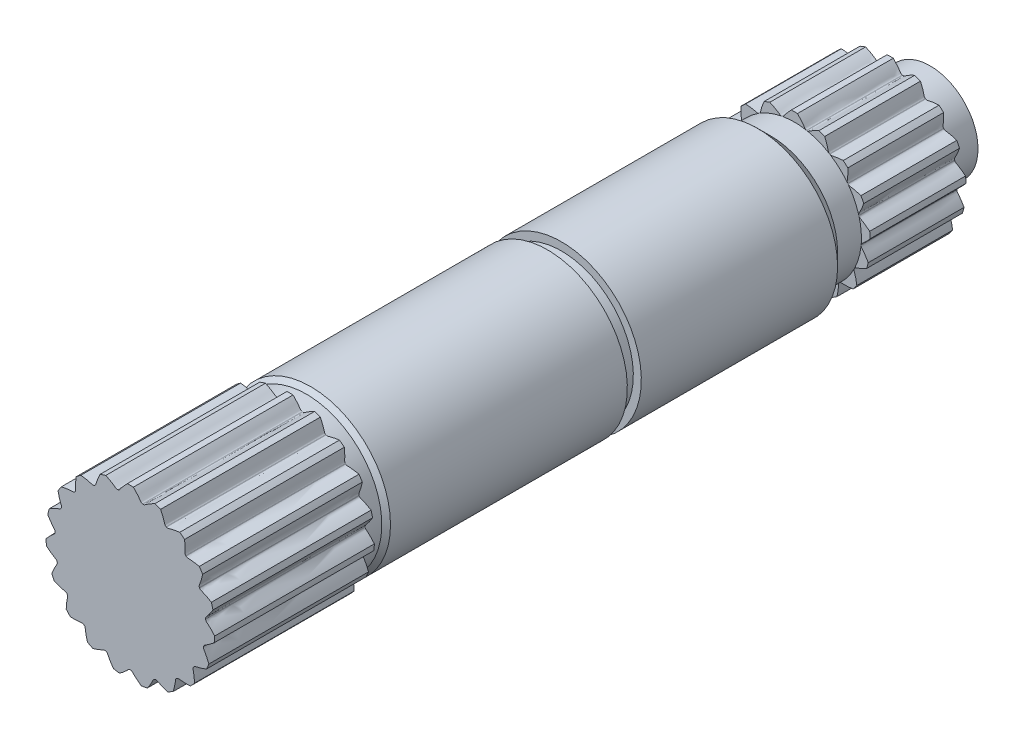
SolidWorks part; units mm, degrees
material "Alloy Steel"
ref_plane "Front Plane" through (0, 0, 0) normal (0, 0, 1) x (1, 0, 0)
ref_plane "Top Plane" through (0, 0, 0) normal (0, 1, 0) x (1, 0, 0)
ref_plane "Right Plane" through (0, 0, 0) normal (1, 0, 0) x (0, 0, -1)
sketch "Sketch12" plane through (0, 0, 0) normal (0, 0, 1) x (1, 0, 0)
  circle A0 centre (0, 0) radius 10
  dimension "D1" = 20
extrude "Shaft" add sketch "Sketch12" along normal mid plane 60
sketch "Sketch13" plane through (0, 0, 30) normal (0, 0, 1) x (1, 0, 0)
  circle A0 centre (0, 0) radius 9.4556
  dimension "D1" = 18.9113
extrude "Motor side relief" add sketch "Sketch13" along normal blind 1.587
sketch "Sketch14" plane through (0, 0, -30) normal (0, 0, -1) x (-1, 0, 0)
  circle A0 centre (0, 0) radius 8.3981
  dimension "D1" = 16.7963
extrude "Gear side relief" add sketch "Sketch14" along normal blind 1.587
sketch "Sketch15" plane through (0, 0, 31.587) normal (0, 0, 1) x (1, 0, 0)
  line L0 (5.7898, -7.4758) -> (5.8078, -7.4618)
  line L1 (5.8078, -7.4618) -> (5.8257, -7.4478)
  line L2 (7.9035, -5.1908) -> (7.9159, -5.1717)
  line L3 (7.9159, -5.1717) -> (7.9284, -5.1527)
  line L4 (9.1607, -2.3432) -> (9.1663, -2.3212)
  line L5 (9.1663, -2.3212) -> (9.1719, -2.2992)
  line L6 (9.4252, 0.7582) -> (9.4233, 0.7808)
  line L7 (9.4233, 0.7808) -> (9.4214, 0.8035)
  line L8 (8.6683, 3.7775) -> (8.6592, 3.7983)
  line L9 (8.6592, 3.7983) -> (8.6501, 3.8191)
  line L10 (6.9721, 6.3874) -> (6.9567, 6.4041)
  line L11 (6.9567, 6.4041) -> (6.9413, 6.4208)
  line L12 (4.5204, 8.3051) -> (4.5004, 8.316)
  line L13 (4.5004, 8.316) -> (4.4804, 8.3268)
  line L14 (1.5788, 9.3229) -> (1.5563, 9.3267)
  line L15 (1.5563, 9.3267) -> (1.5339, 9.3304)
  line L16 (-1.5339, 9.3304) -> (-1.5563, 9.3267)
  line L17 (-1.5563, 9.3267) -> (-1.5788, 9.3229)
  line L18 (-4.4804, 8.3268) -> (-4.5004, 8.316)
  line L19 (-4.5004, 8.316) -> (-4.5204, 8.3051)
  line L20 (-6.9413, 6.4208) -> (-6.9567, 6.4041)
  line L21 (-6.9567, 6.4041) -> (-6.9721, 6.3874)
  line L22 (-8.6501, 3.8191) -> (-8.6592, 3.7983)
  line L23 (-8.6592, 3.7983) -> (-8.6683, 3.7775)
  line L24 (-9.4214, 0.8035) -> (-9.4233, 0.7808)
  line L25 (-9.4233, 0.7808) -> (-9.4252, 0.7582)
  line L26 (-9.1719, -2.2992) -> (-9.1663, -2.3212)
  line L27 (-9.1663, -2.3212) -> (-9.1607, -2.3432)
  line L28 (-7.9284, -5.1527) -> (-7.9159, -5.1717)
  line L29 (-7.9159, -5.1717) -> (-7.9035, -5.1908)
  line L30 (-5.8257, -7.4478) -> (-5.8078, -7.4618)
  line L31 (-5.8078, -7.4618) -> (-5.7898, -7.4758)
  line L32 (-3.0917, -8.9359) -> (-3.0702, -8.9433)
  line L33 (-3.0702, -8.9433) -> (-3.0487, -8.9507)
  line L34 (-0.0227, -9.4556) -> (0, -9.4556)
  line L35 (0, -9.4556) -> (0.0227, -9.4556)
  line L36 (3.0487, -8.9507) -> (3.0702, -8.9433)
  line L37 (3.0702, -8.9433) -> (3.0917, -8.9359)
  arc A0 (4.6925, -9.4774) -> (5.3676, -9.1121) centre (0, 0) ccw
  arc A1 (7.5156, -7.4402) -> (8.0355, -6.8755) centre (0, 0) ccw
  arc A2 (9.5242, -4.5968) -> (9.8326, -3.8939) centre (0, 0) ccw
  arc A3 (10.5007, -1.2552) -> (10.5641, -0.4903) centre (0, 0) ccw
  arc A4 (10.3394, 2.2224) -> (10.1509, 2.9665) centre (0, 0) ccw
  arc A5 (9.0575, 5.4591) -> (8.6377, 6.1017) centre (0, 0) ccw
  arc A6 (6.7942, 8.1043) -> (6.1885, 8.5758) centre (0, 0) ccw
  arc A7 (3.7946, 9.8713) -> (3.0686, 10.1205) centre (0, 0) ccw
  arc A8 (0.3838, 10.5685) -> (-0.3838, 10.5685) centre (0, 0) ccw
  arc A9 (-3.0686, 10.1205) -> (-3.7946, 9.8713) centre (0, 0) ccw
  arc A10 (-6.1885, 8.5758) -> (-6.7942, 8.1043) centre (0, 0) ccw
  arc A11 (-8.6377, 6.1017) -> (-9.0575, 5.4591) centre (0, 0) ccw
  arc A12 (-10.1509, 2.9665) -> (-10.3394, 2.2224) centre (0, 0) ccw
  arc A13 (-10.5641, -0.4903) -> (-10.5007, -1.2552) centre (0, 0) ccw
  arc A14 (-9.8326, -3.8939) -> (-9.5242, -4.5968) centre (0, 0) ccw
  arc A15 (-8.0355, -6.8755) -> (-7.5156, -7.4402) centre (0, 0) ccw
  arc A16 (-5.3676, -9.1121) -> (-4.6925, -9.4774) centre (0, 0) ccw
  arc A17 (-2.1181, -10.3612) -> (-1.361, -10.4876) centre (0, 0) ccw
  arc A18 (1.361, -10.4876) -> (2.1181, -10.3612) centre (0, 0) ccw
  spline S0 degree 3 poles (3.0917, -8.9359) (3.1544, -8.9142) (3.2184, -8.911) (3.3396, -8.938) (3.397, -8.9729) (3.5767, -9.0624) (3.828, -9.1783) (4.24, -9.3384) (4.5379, -9.4334) (4.6925, -9.4774) knots 0 0 0 0 0.125 0.125 0.25 0.25 0.5 0.75 1 1 1 1
  spline S1 degree 3 poles (5.3676, -9.1121) (5.4153, -8.9586) (5.4987, -8.6572) (5.5901, -8.2247) (5.6305, -7.951) (5.6538, -7.7516) (5.656, -7.6845) (5.6997, -7.5682) (5.7374, -7.5164) (5.7898, -7.4758) knots 0 0 0 0 0.25 0.5 0.75 0.75 0.875 0.875 1 1 1 1
  spline S2 degree 3 poles (5.8257, -7.4478) (5.8779, -7.407) (5.9374, -7.3832) (6.0608, -7.3694) (6.1265, -7.3837) (6.3255, -7.41) (6.6008, -7.438) (7.0425, -7.4557) (7.3551, -7.4488) (7.5156, -7.4402) knots 0 0 0 0 0.125 0.125 0.25 0.25 0.5 0.75 1 1 1 1
  spline S3 degree 3 poles (8.0355, -6.8755) (8.0308, -6.7148) (8.0117, -6.4027) (7.9577, -5.964) (7.9071, -5.692) (7.8645, -5.4958) (7.8447, -5.4316) (7.8483, -5.3075) (7.8671, -5.2462) (7.9035, -5.1908) knots 0 0 0 0 0.25 0.5 0.75 0.75 0.875 0.875 1 1 1 1
  spline S4 degree 3 poles (7.9284, -5.1527) (7.9645, -5.0971) (8.013, -5.0552) (8.1253, -5.0021) (8.192, -4.9944) (8.3888, -4.9546) (8.6583, -4.8918) (9.0817, -4.765) (9.3752, -4.6571) (9.5242, -4.5968) knots 0 0 0 0 0.125 0.125 0.25 0.25 0.5 0.75 1 1 1 1
  spline S5 degree 3 poles (9.8326, -3.8939) (9.7759, -3.7434) (9.6566, -3.4544) (9.4631, -3.057) (9.3268, -2.8161) (9.2228, -2.6445) (9.1833, -2.5901) (9.1463, -2.4716) (9.1443, -2.4075) (9.1607, -2.3432) knots 0 0 0 0 0.25 0.5 0.75 0.75 0.875 0.875 1 1 1 1
  spline S6 degree 3 poles (9.1719, -2.2992) (9.188, -2.2349) (9.2203, -2.1795) (9.3092, -2.0928) (9.3699, -2.0638) (9.543, -1.9624) (9.7775, -1.8154) (10.1368, -1.558) (10.3793, -1.3606) (10.5007, -1.2552) knots 0 0 0 0 0.125 0.125 0.25 0.25 0.5 0.75 1 1 1 1
  spline S7 degree 3 poles (10.5641, -0.4903) (10.4617, -0.3663) (10.255, -0.1317) (9.9429, 0.1813) (9.7359, 0.3649) (9.5818, 0.4935) (9.5267, 0.532) (9.4533, 0.6322) (9.4305, 0.6921) (9.4252, 0.7582) knots 0 0 0 0 0.25 0.5 0.75 0.75 0.875 0.875 1 1 1 1
  spline S8 degree 3 poles (9.4214, 0.8035) (9.4158, 0.8695) (9.4284, 0.9324) (9.4844, 1.0433) (9.5323, 1.0904) (9.6631, 1.2426) (9.8372, 1.4577) (10.0935, 1.8179) (10.2588, 2.0833) (10.3394, 2.2224) knots 0 0 0 0 0.125 0.125 0.25 0.25 0.5 0.75 1 1 1 1
  spline S9 degree 3 poles (10.1509, 2.9665) (10.0138, 3.0504) (9.7422, 3.2052) (9.3453, 3.4) (9.0899, 3.5063) (8.9024, 3.5779) (8.8378, 3.5965) (8.7358, 3.6674) (8.6948, 3.7167) (8.6683, 3.7775) knots 0 0 0 0 0.25 0.5 0.75 0.75 0.875 0.875 1 1 1 1
  spline S10 degree 3 poles (8.6501, 3.8191) (8.6233, 3.8797) (8.6148, 3.9433) (8.6317, 4.0663) (8.6618, 4.1264) (8.7361, 4.3129) (8.8308, 4.5729) (8.9563, 4.9967) (9.0265, 5.3014) (9.0575, 5.4591) knots 0 0 0 0 0.125 0.125 0.25 0.25 0.5 0.75 1 1 1 1
  spline S11 degree 3 poles (8.6377, 6.1017) (8.4808, 6.1366) (8.1736, 6.1948) (7.735, 6.2502) (7.4588, 6.2678) (7.2583, 6.2747) (7.1911, 6.2713) (7.0717, 6.3052) (7.0169, 6.3385) (6.9721, 6.3874) knots 0 0 0 0 0.25 0.5 0.75 0.75 0.875 0.875 1 1 1 1
  spline S12 degree 3 poles (6.9413, 6.4208) (6.8963, 6.4695) (6.8676, 6.5268) (6.8437, 6.6487) (6.8526, 6.7153) (6.8624, 6.9158) (6.8676, 7.1925) (6.8486, 7.6341) (6.816, 7.9451) (6.7942, 8.1043) knots 0 0 0 0 0.125 0.125 0.25 0.25 0.5 0.75 1 1 1 1
  spline S13 degree 3 poles (6.1885, 8.5758) (6.0287, 8.5578) (5.7193, 8.5131) (5.2865, 8.4231) (5.0196, 8.3501) (4.8276, 8.2914) (4.7652, 8.2664) (4.6412, 8.2597) (4.5786, 8.2734) (4.5204, 8.3051) knots 0 0 0 0 0.25 0.5 0.75 0.75 0.875 0.875 1 1 1 1
  spline S14 degree 3 poles (4.4804, 8.3268) (4.422, 8.3582) (4.3763, 8.4031) (4.3141, 8.5106) (4.3009, 8.5765) (4.245, 8.7693) (4.1601, 9.0326) (3.9988, 9.4442) (3.8669, 9.7277) (3.7946, 9.8713) knots 0 0 0 0 0.125 0.125 0.25 0.25 0.5 0.75 1 1 1 1
  spline S15 degree 3 poles (3.0686, 10.1205) (2.9233, 10.0517) (2.6452, 9.9089) (2.2651, 9.6832) (2.0363, 9.5275) (1.8738, 9.4097) (1.8229, 9.3658) (1.7078, 9.3192) (1.6441, 9.3118) (1.5788, 9.3229) knots 0 0 0 0 0.25 0.5 0.75 0.75 0.875 0.875 1 1 1 1
  spline S16 degree 3 poles (1.5339, 9.3304) (1.4685, 9.3411) (1.4107, 9.3688) (1.3169, 9.4502) (1.283, 9.5083) (1.1676, 9.6725) (1.0018, 9.894) (0.7156, 10.2309) (0.4988, 10.4563) (0.3838, 10.5685) knots 0 0 0 0 0.125 0.125 0.25 0.25 0.5 0.75 1 1 1 1
  spline S17 degree 3 poles (-0.3838, 10.5685) (-0.4988, 10.4563) (-0.7156, 10.2309) (-1.0018, 9.894) (-1.1676, 9.6725) (-1.283, 9.5083) (-1.3169, 9.4502) (-1.4107, 9.3688) (-1.4685, 9.3411) (-1.5339, 9.3304) knots 0 0 0 0 0.25 0.5 0.75 0.75 0.875 0.875 1 1 1 1
  spline S18 degree 3 poles (-1.5788, 9.3229) (-1.6441, 9.3118) (-1.7078, 9.3192) (-1.8229, 9.3658) (-1.8738, 9.4097) (-2.0363, 9.5275) (-2.2651, 9.6832) (-2.6452, 9.9089) (-2.9233, 10.0517) (-3.0686, 10.1205) knots 0 0 0 0 0.125 0.125 0.25 0.25 0.5 0.75 1 1 1 1
  spline S19 degree 3 poles (-3.7946, 9.8713) (-3.8669, 9.7277) (-3.9988, 9.4442) (-4.1601, 9.0326) (-4.245, 8.7693) (-4.3009, 8.5765) (-4.3141, 8.5106) (-4.3763, 8.4031) (-4.422, 8.3582) (-4.4804, 8.3268) knots 0 0 0 0 0.25 0.5 0.75 0.75 0.875 0.875 1 1 1 1
  spline S20 degree 3 poles (-4.5204, 8.3051) (-4.5786, 8.2734) (-4.6412, 8.2597) (-4.7652, 8.2664) (-4.8276, 8.2914) (-5.0196, 8.3501) (-5.2865, 8.4231) (-5.7193, 8.5131) (-6.0287, 8.5578) (-6.1885, 8.5758) knots 0 0 0 0 0.125 0.125 0.25 0.25 0.5 0.75 1 1 1 1
  spline S21 degree 3 poles (-6.7942, 8.1043) (-6.816, 7.9451) (-6.8486, 7.6341) (-6.8676, 7.1925) (-6.8624, 6.9158) (-6.8526, 6.7153) (-6.8437, 6.6487) (-6.8676, 6.5268) (-6.8963, 6.4695) (-6.9413, 6.4208) knots 0 0 0 0 0.25 0.5 0.75 0.75 0.875 0.875 1 1 1 1
  spline S22 degree 3 poles (-6.9721, 6.3874) (-7.0169, 6.3385) (-7.0717, 6.3052) (-7.1911, 6.2713) (-7.2583, 6.2747) (-7.4588, 6.2678) (-7.735, 6.2502) (-8.1736, 6.1948) (-8.4808, 6.1366) (-8.6377, 6.1017) knots 0 0 0 0 0.125 0.125 0.25 0.25 0.5 0.75 1 1 1 1
  spline S23 degree 3 poles (-9.0575, 5.4591) (-9.0265, 5.3014) (-8.9563, 4.9967) (-8.8308, 4.5729) (-8.7361, 4.3129) (-8.6618, 4.1264) (-8.6317, 4.0663) (-8.6148, 3.9433) (-8.6233, 3.8797) (-8.6501, 3.8191) knots 0 0 0 0 0.25 0.5 0.75 0.75 0.875 0.875 1 1 1 1
  spline S24 degree 3 poles (-8.6683, 3.7775) (-8.6948, 3.7167) (-8.7358, 3.6674) (-8.8378, 3.5965) (-8.9024, 3.5779) (-9.0899, 3.5063) (-9.3453, 3.4) (-9.7422, 3.2052) (-10.0138, 3.0504) (-10.1509, 2.9665) knots 0 0 0 0 0.125 0.125 0.25 0.25 0.5 0.75 1 1 1 1
  spline S25 degree 3 poles (-10.3394, 2.2224) (-10.2588, 2.0833) (-10.0935, 1.8179) (-9.8372, 1.4577) (-9.6631, 1.2426) (-9.5323, 1.0904) (-9.4844, 1.0433) (-9.4284, 0.9324) (-9.4158, 0.8695) (-9.4214, 0.8035) knots 0 0 0 0 0.25 0.5 0.75 0.75 0.875 0.875 1 1 1 1
  spline S26 degree 3 poles (-9.4252, 0.7582) (-9.4305, 0.6921) (-9.4533, 0.6322) (-9.5267, 0.532) (-9.5818, 0.4935) (-9.7359, 0.3649) (-9.9429, 0.1813) (-10.255, -0.1317) (-10.4617, -0.3663) (-10.5641, -0.4903) knots 0 0 0 0 0.125 0.125 0.25 0.25 0.5 0.75 1 1 1 1
  spline S27 degree 3 poles (-10.5007, -1.2552) (-10.3793, -1.3606) (-10.1368, -1.558) (-9.7775, -1.8154) (-9.543, -1.9624) (-9.3699, -2.0638) (-9.3092, -2.0928) (-9.2203, -2.1795) (-9.188, -2.2349) (-9.1719, -2.2992) knots 0 0 0 0 0.25 0.5 0.75 0.75 0.875 0.875 1 1 1 1
  spline S28 degree 3 poles (-9.1607, -2.3432) (-9.1443, -2.4075) (-9.1463, -2.4716) (-9.1833, -2.5901) (-9.2228, -2.6445) (-9.3268, -2.8161) (-9.4631, -3.057) (-9.6566, -3.4544) (-9.7759, -3.7434) (-9.8326, -3.8939) knots 0 0 0 0 0.125 0.125 0.25 0.25 0.5 0.75 1 1 1 1
  spline S29 degree 3 poles (-9.5242, -4.5968) (-9.3752, -4.6571) (-9.0817, -4.765) (-8.6583, -4.8918) (-8.3888, -4.9546) (-8.192, -4.9944) (-8.1253, -5.0021) (-8.013, -5.0552) (-7.9645, -5.0971) (-7.9284, -5.1527) knots 0 0 0 0 0.25 0.5 0.75 0.75 0.875 0.875 1 1 1 1
  spline S30 degree 3 poles (-7.9035, -5.1908) (-7.8671, -5.2462) (-7.8483, -5.3075) (-7.8447, -5.4316) (-7.8645, -5.4958) (-7.9071, -5.692) (-7.9577, -5.964) (-8.0117, -6.4027) (-8.0308, -6.7148) (-8.0355, -6.8755) knots 0 0 0 0 0.125 0.125 0.25 0.25 0.5 0.75 1 1 1 1
  spline S31 degree 3 poles (-7.5156, -7.4402) (-7.3551, -7.4488) (-7.0425, -7.4557) (-6.6008, -7.438) (-6.3255, -7.41) (-6.1265, -7.3837) (-6.0608, -7.3694) (-5.9374, -7.3832) (-5.8779, -7.407) (-5.8257, -7.4478) knots 0 0 0 0 0.25 0.5 0.75 0.75 0.875 0.875 1 1 1 1
  spline S32 degree 3 poles (-5.7898, -7.4758) (-5.7374, -7.5164) (-5.6997, -7.5682) (-5.656, -7.6845) (-5.6538, -7.7516) (-5.6305, -7.951) (-5.5901, -8.2247) (-5.4987, -8.6572) (-5.4153, -8.9586) (-5.3676, -9.1121) knots 0 0 0 0 0.125 0.125 0.25 0.25 0.5 0.75 1 1 1 1
  spline S33 degree 3 poles (-4.6925, -9.4774) (-4.5379, -9.4334) (-4.24, -9.3384) (-3.828, -9.1783) (-3.5767, -9.0624) (-3.397, -8.9729) (-3.3396, -8.938) (-3.2184, -8.911) (-3.1544, -8.9142) (-3.0917, -8.9359) knots 0 0 0 0 0.25 0.5 0.75 0.75 0.875 0.875 1 1 1 1
  spline S34 degree 3 poles (-3.0487, -8.9507) (-2.986, -8.972) (-2.9335, -9.0088) (-2.8544, -9.1046) (-2.8306, -9.1674) (-2.7437, -9.3484) (-2.6166, -9.5942) (-2.3898, -9.9736) (-2.2131, -10.2315) (-2.1181, -10.3612) knots 0 0 0 0 0.125 0.125 0.25 0.25 0.5 0.75 1 1 1 1
  spline S35 degree 3 poles (-1.361, -10.4876) (-1.229, -10.3957) (-0.9781, -10.2091) (-0.6404, -9.9239) (-0.4404, -9.7327) (-0.2995, -9.5898) (-0.2565, -9.5381) (-0.1506, -9.4732) (-0.089, -9.4555) (-0.0227, -9.4556) knots 0 0 0 0 0.25 0.5 0.75 0.75 0.875 0.875 1 1 1 1
  spline S36 degree 3 poles (0.0227, -9.4556) (0.089, -9.4555) (0.1506, -9.4732) (0.2565, -9.5381) (0.2995, -9.5898) (0.4404, -9.7327) (0.6404, -9.9239) (0.9781, -10.2091) (1.229, -10.3957) (1.361, -10.4876) knots 0 0 0 0 0.125 0.125 0.25 0.25 0.5 0.75 1 1 1 1
  spline S37 degree 3 poles (2.1181, -10.3612) (2.2131, -10.2315) (2.3898, -9.9736) (2.6166, -9.5942) (2.7437, -9.3484) (2.8306, -9.1674) (2.8544, -9.1046) (2.9335, -9.0088) (2.986, -8.972) (3.0487, -8.9507) knots 0 0 0 0 0.25 0.5 0.75 0.75 0.875 0.875 1 1 1 1
extrude "Boss-Extrude8" add sketch "Sketch15" along normal blind 20
sketch "Sketch17" plane through (0, 0, -31.587) normal (0, 0, -1) x (-1, 0, 0)
  line L38 (4.4402, 7.1283) -> (4.4211, 7.1402)
  line L39 (4.4211, 7.1402) -> (4.4019, 7.1521)
  line L40 (1.5653, 8.251) -> (1.5432, 8.2552)
  line L41 (1.5432, 8.2552) -> (1.521, 8.2593)
  line L42 (-1.521, 8.2593) -> (-1.5432, 8.2552)
  line L43 (-1.5432, 8.2552) -> (-1.5653, 8.251)
  line L44 (-4.4019, 7.1521) -> (-4.4211, 7.1402)
  line L45 (-4.4211, 7.1402) -> (-4.4402, 7.1283)
  line L46 (-6.6882, 5.079) -> (-6.7019, 5.061)
  line L47 (-6.7019, 5.061) -> (-6.7154, 5.043)
  line L48 (-8.0713, 2.32) -> (-8.0776, 2.2983)
  line L49 (-8.0776, 2.2983) -> (-8.0837, 2.2766)
  line L50 (-8.3644, -0.7524) -> (-8.3623, -0.7749)
  line L51 (-8.3623, -0.7749) -> (-8.3602, -0.7973)
  line L52 (-7.5277, -3.7232) -> (-7.5177, -3.7434)
  line L53 (-7.5177, -3.7434) -> (-7.5076, -3.7636)
  line L54 (-5.6744, -6.1911) -> (-5.6578, -6.2063)
  line L55 (-5.6578, -6.2063) -> (-5.6411, -6.2215)
  line L56 (-3.0548, -7.8229) -> (-3.0338, -7.831)
  line L57 (-3.0338, -7.831) -> (-3.0127, -7.8392)
  line L58 (-0.0226, -8.3981) -> (0, -8.3981)
  line L59 (0, -8.3981) -> (0.0226, -8.3981)
  line L60 (3.0127, -7.8392) -> (3.0338, -7.831)
  line L61 (3.0338, -7.831) -> (3.0548, -7.8229)
  line L62 (5.6411, -6.2215) -> (5.6578, -6.2063)
  line L63 (5.6578, -6.2063) -> (5.6744, -6.1911)
  line L64 (7.5076, -3.7636) -> (7.5177, -3.7434)
  line L65 (7.5177, -3.7434) -> (7.5277, -3.7232)
  line L66 (8.3602, -0.7973) -> (8.3623, -0.7749)
  line L67 (8.3623, -0.7749) -> (8.3644, -0.7524)
  line L68 (8.0837, 2.2766) -> (8.0776, 2.2983)
  line L69 (8.0776, 2.2983) -> (8.0713, 2.32)
  line L70 (6.7154, 5.043) -> (6.7019, 5.061)
  line L71 (6.7019, 5.061) -> (6.6882, 5.079)
  arc A19 (6.6912, 6.7683) -> (6.1221, 7.2872) centre (0, 0) ccw
  arc A20 (3.7944, 8.7284) -> (3.0762, 9.0066) centre (0, 0) ccw
  arc A21 (0.3851, 9.5097) -> (-0.3851, 9.5097) centre (0, 0) ccw
  arc A22 (-3.0762, 9.0066) -> (-3.7944, 8.7284) centre (0, 0) ccw
  arc A23 (-6.1221, 7.2872) -> (-6.6912, 6.7683) centre (0, 0) ccw
  arc A24 (-8.3411, 4.5835) -> (-8.6844, 3.8941) centre (0, 0) ccw
  arc A25 (-9.4336, 1.2609) -> (-9.5047, 0.494) centre (0, 0) ccw
  arc A26 (-9.2521, -2.2321) -> (-9.0413, -2.9728) centre (0, 0) ccw
  arc A27 (-7.821, -5.4236) -> (-7.3569, -6.0382) centre (0, 0) ccw
  arc A28 (-5.3336, -7.8826) -> (-4.6788, -8.288) centre (0, 0) ccw
  arc A29 (-2.1259, -9.277) -> (-1.3689, -9.4185) centre (0, 0) ccw
  arc A30 (1.3689, -9.4185) -> (2.1259, -9.277) centre (0, 0) ccw
  arc A31 (4.6788, -8.288) -> (5.3336, -7.8826) centre (0, 0) ccw
  arc A32 (7.3569, -6.0382) -> (7.821, -5.4236) centre (0, 0) ccw
  arc A33 (9.0413, -2.9728) -> (9.2521, -2.2321) centre (0, 0) ccw
  arc A34 (9.5047, 0.494) -> (9.4336, 1.2609) centre (0, 0) ccw
  arc A35 (8.6844, 3.8941) -> (8.3411, 4.5835) centre (0, 0) ccw
  spline S0 degree 3 poles (6.6882, 5.079) (6.6486, 5.1312) (6.6257, 5.1903) (6.6128, 5.3124) (6.6277, 5.3769) (6.657, 5.5736) (6.6884, 5.8472) (6.7084, 6.2901) (6.7009, 6.6058) (6.6912, 6.7683) knots 0 0 0 0 0.125 0.125 0.25 0.25 0.5 0.75 1 1 1 1 weights 1 1 1 1 1 1 1 1 1 1
  spline S1 degree 3 poles (6.1221, 7.2872) (5.9593, 7.2818) (5.6443, 7.2602) (5.2052, 7.1994) (4.9356, 7.1428) (4.7425, 7.0956) (4.6796, 7.0748) (4.5569, 7.0763) (4.4958, 7.0937) (4.4402, 7.1283) knots 0 0 0 0 0.25 0.5 0.75 0.75 0.875 0.875 1 1 1 1 weights 1 1 1 1 1 1 1 1 1 1
  spline S2 degree 3 poles (4.4019, 7.1521) (4.3461, 7.1864) (4.3033, 7.2333) (4.2472, 7.3425) (4.2378, 7.4081) (4.194, 7.602) (4.1245, 7.8685) (3.9832, 8.2887) (3.8621, 8.5804) (3.7944, 8.7284) knots 0 0 0 0 0.125 0.125 0.25 0.25 0.5 0.75 1 1 1 1 weights 1 1 1 1 1 1 1 1 1 1
  spline S3 degree 3 poles (3.0762, 9.0066) (2.9264, 8.9428) (2.6405, 8.8089) (2.253, 8.5935) (2.022, 8.4434) (1.859, 8.3296) (1.8079, 8.2875) (1.6929, 8.2446) (1.6297, 8.2388) (1.5653, 8.251) knots 0 0 0 0 0.25 0.5 0.75 0.75 0.875 0.875 1 1 1 1 weights 1 1 1 1 1 1 1 1 1 1
  spline S4 degree 3 poles (1.521, 8.2593) (1.4566, 8.2711) (1.3997, 8.2994) (1.308, 8.3809) (1.2755, 8.4387) (1.1646, 8.6037) (1.0035, 8.8271) (0.7199, 9.1679) (0.5017, 9.3961) (0.3851, 9.5097) knots 0 0 0 0 0.125 0.125 0.25 0.25 0.5 0.75 1 1 1 1 weights 1 1 1 1 1 1 1 1 1 1
  spline S5 degree 3 poles (-0.3851, 9.5097) (-0.5017, 9.3961) (-0.7199, 9.1679) (-1.0035, 8.8271) (-1.1646, 8.6037) (-1.2755, 8.4387) (-1.308, 8.3809) (-1.3997, 8.2994) (-1.4566, 8.2711) (-1.521, 8.2593) knots 0 0 0 0 0.25 0.5 0.75 0.75 0.875 0.875 1 1 1 1 weights 1 1 1 1 1 1 1 1 1 1
  spline S6 degree 3 poles (-1.5653, 8.251) (-1.6297, 8.2388) (-1.6929, 8.2446) (-1.8079, 8.2875) (-1.859, 8.3296) (-2.022, 8.4434) (-2.253, 8.5935) (-2.6405, 8.8089) (-2.9264, 8.9428) (-3.0762, 9.0066) knots 0 0 0 0 0.125 0.125 0.25 0.25 0.5 0.75 1 1 1 1 weights 1 1 1 1 1 1 1 1 1 1
  spline S7 degree 3 poles (-3.7944, 8.7284) (-3.8621, 8.5804) (-3.9832, 8.2887) (-4.1245, 7.8685) (-4.194, 7.602) (-4.2378, 7.4081) (-4.2472, 7.3425) (-4.3033, 7.2333) (-4.3461, 7.1864) (-4.4019, 7.1521) knots 0 0 0 0 0.25 0.5 0.75 0.75 0.875 0.875 1 1 1 1 weights 1 1 1 1 1 1 1 1 1 1
  spline S8 degree 3 poles (-4.4402, 7.1283) (-4.4958, 7.0937) (-4.5569, 7.0763) (-4.6796, 7.0748) (-4.7425, 7.0956) (-4.9356, 7.1428) (-5.2052, 7.1994) (-5.6443, 7.2602) (-5.9593, 7.2818) (-6.1221, 7.2872) knots 0 0 0 0 0.125 0.125 0.25 0.25 0.5 0.75 1 1 1 1 weights 1 1 1 1 1 1 1 1 1 1
  spline S9 degree 3 poles (-6.6912, 6.7683) (-6.7009, 6.6058) (-6.7084, 6.2901) (-6.6884, 5.8472) (-6.657, 5.5736) (-6.6277, 5.3769) (-6.6128, 5.3124) (-6.6257, 5.1903) (-6.6486, 5.1312) (-6.6882, 5.079) knots 0 0 0 0 0.25 0.5 0.75 0.75 0.875 0.875 1 1 1 1 weights 1 1 1 1 1 1 1 1 1 1
  spline S10 degree 3 poles (-6.7154, 5.043) (-6.7548, 4.9906) (-6.8054, 4.9523) (-6.9193, 4.9066) (-6.9854, 4.9033) (-7.1826, 4.8775) (-7.4544, 4.8329) (-7.8859, 4.7309) (-8.1874, 4.6373) (-8.3411, 4.5835) knots 0 0 0 0 0.125 0.125 0.25 0.25 0.5 0.75 1 1 1 1 weights 1 1 1 1 1 1 1 1 1 1
  spline S11 degree 3 poles (-8.6844, 3.8941) (-8.6347, 3.7391) (-8.5277, 3.442) (-8.349, 3.0363) (-8.2209, 2.7925) (-8.1225, 2.6196) (-8.0853, 2.5648) (-8.0532, 2.4464) (-8.0533, 2.3829) (-8.0713, 2.32) knots 0 0 0 0 0.25 0.5 0.75 0.75 0.875 0.875 1 1 1 1 weights 1 1 1 1 1 1 1 1 1 1
  spline S12 degree 3 poles (-8.0837, 2.2766) (-8.1015, 2.2135) (-8.1348, 2.1595) (-8.2245, 2.0757) (-8.285, 2.0487) (-8.4596, 1.9535) (-8.6968, 1.8137) (-9.0624, 1.5628) (-9.3097, 1.3665) (-9.4336, 1.2609) knots 0 0 0 0 0.125 0.125 0.25 0.25 0.5 0.75 1 1 1 1 weights 1 1 1 1 1 1 1 1 1 1
  spline S13 degree 3 poles (-9.5047, 0.494) (-9.4023, 0.3674) (-9.1952, 0.129) (-8.882, -0.1848) (-8.6745, -0.3658) (-8.5204, -0.4915) (-8.4659, -0.5291) (-8.3931, -0.628) (-8.3702, -0.6872) (-8.3644, -0.7524) knots 0 0 0 0 0.25 0.5 0.75 0.75 0.875 0.875 1 1 1 1 weights 1 1 1 1 1 1 1 1 1 1
  spline S14 degree 3 poles (-8.3602, -0.7973) (-8.354, -0.8625) (-8.3656, -0.925) (-8.419, -1.0355) (-8.4656, -1.0825) (-8.594, -1.2344) (-8.7647, -1.4504) (-9.0149, -1.8164) (-9.1747, -2.0888) (-9.2521, -2.2321) knots 0 0 0 0 0.125 0.125 0.25 0.25 0.5 0.75 1 1 1 1 weights 1 1 1 1 1 1 1 1 1 1
  spline S15 degree 3 poles (-9.0413, -2.9728) (-8.9001, -3.0539) (-8.6209, -3.2014) (-8.2155, -3.3809) (-7.9566, -3.4747) (-7.7675, -3.5362) (-7.7031, -3.5516) (-7.5995, -3.6175) (-7.5568, -3.6645) (-7.5277, -3.7232) knots 0 0 0 0 0.25 0.5 0.75 0.75 0.875 0.875 1 1 1 1 weights 1 1 1 1 1 1 1 1 1 1
  spline S16 degree 3 poles (-7.5076, -3.7636) (-7.4783, -3.8221) (-7.4666, -3.8845) (-7.4764, -4.0068) (-7.5029, -4.0675) (-7.5678, -4.2555) (-7.6489, -4.5187) (-7.75, -4.9504) (-7.8006, -5.262) (-7.821, -5.4236) knots 0 0 0 0 0.125 0.125 0.25 0.25 0.5 0.75 1 1 1 1 weights 1 1 1 1 1 1 1 1 1 1
  spline S17 degree 3 poles (-7.3569, -6.0382) (-7.1959, -6.0628) (-6.8823, -6.0994) (-6.4394, -6.1203) (-6.1641, -6.1143) (-5.9655, -6.1033) (-5.8999, -6.0945) (-5.7795, -6.1185) (-5.7227, -6.1468) (-5.6744, -6.1911) knots 0 0 0 0 0.25 0.5 0.75 0.75 0.875 0.875 1 1 1 1 weights 1 1 1 1 1 1 1 1 1 1
  spline S18 degree 3 poles (-5.6411, -6.2215) (-5.5926, -6.2655) (-5.5591, -6.3194) (-5.5241, -6.437) (-5.5269, -6.5032) (-5.5195, -6.7019) (-5.5001, -6.9766) (-5.4384, -7.4157) (-5.373, -7.7246) (-5.3336, -7.8826) knots 0 0 0 0 0.125 0.125 0.25 0.25 0.5 0.75 1 1 1 1 weights 1 1 1 1 1 1 1 1 1 1
  spline S19 degree 3 poles (-4.6788, -8.288) (-4.5198, -8.2528) (-4.2142, -8.1737) (-3.7936, -8.0332) (-3.5391, -7.9281) (-3.3579, -7.8462) (-3.2999, -7.8142) (-3.179, -7.7931) (-3.1158, -7.799) (-3.0548, -7.8229) knots 0 0 0 0 0.25 0.5 0.75 0.75 0.875 0.875 1 1 1 1 weights 1 1 1 1 1 1 1 1 1 1
  spline S20 degree 3 poles (-3.0127, -7.8392) (-2.9516, -7.8627) (-2.9009, -7.9009) (-2.8257, -7.9979) (-2.8044, -8.0606) (-2.7257, -8.2432) (-2.6084, -8.4924) (-2.3923, -8.8795) (-2.2197, -9.1439) (-2.1259, -9.277) knots 0 0 0 0 0.125 0.125 0.25 0.25 0.5 0.75 1 1 1 1 weights 1 1 1 1 1 1 1 1 1 1
  spline S21 degree 3 poles (-1.3689, -9.4185) (-1.2333, -9.3283) (-0.9769, -9.1441) (-0.6355, -8.8612) (-0.4361, -8.6712) (-0.2968, -8.5294) (-0.2543, -8.4786) (-0.1491, -8.4153) (-0.0881, -8.3979) (-0.0226, -8.3981) knots 0 0 0 0 0.25 0.5 0.75 0.75 0.875 0.875 1 1 1 1 weights 1 1 1 1 1 1 1 1 1 1
  spline S22 degree 3 poles (0.0226, -8.3981) (0.0881, -8.3979) (0.1491, -8.4153) (0.2543, -8.4786) (0.2968, -8.5294) (0.4361, -8.6712) (0.6355, -8.8612) (0.9769, -9.1441) (1.2333, -9.3283) (1.3689, -9.4185) knots 0 0 0 0 0.125 0.125 0.25 0.25 0.5 0.75 1 1 1 1 weights 1 1 1 1 1 1 1 1 1 1
  spline S23 degree 3 poles (2.1259, -9.277) (2.2197, -9.1439) (2.3923, -8.8795) (2.6084, -8.4924) (2.7257, -8.2432) (2.8044, -8.0606) (2.8257, -7.9979) (2.9009, -7.9009) (2.9516, -7.8627) (3.0127, -7.8392) knots 0 0 0 0 0.25 0.5 0.75 0.75 0.875 0.875 1 1 1 1 weights 1 1 1 1 1 1 1 1 1 1
  spline S24 degree 3 poles (3.0548, -7.8229) (3.1158, -7.799) (3.179, -7.7931) (3.2999, -7.8142) (3.3579, -7.8462) (3.5391, -7.9281) (3.7936, -8.0332) (4.2142, -8.1737) (4.5198, -8.2528) (4.6788, -8.288) knots 0 0 0 0 0.125 0.125 0.25 0.25 0.5 0.75 1 1 1 1 weights 1 1 1 1 1 1 1 1 1 1
  spline S25 degree 3 poles (5.3336, -7.8826) (5.373, -7.7246) (5.4384, -7.4157) (5.5001, -6.9766) (5.5195, -6.7019) (5.5269, -6.5032) (5.5241, -6.437) (5.5591, -6.3194) (5.5926, -6.2655) (5.6411, -6.2215) knots 0 0 0 0 0.25 0.5 0.75 0.75 0.875 0.875 1 1 1 1 weights 1 1 1 1 1 1 1 1 1 1
  spline S26 degree 3 poles (5.6744, -6.1911) (5.7227, -6.1468) (5.7795, -6.1185) (5.8999, -6.0945) (5.9655, -6.1033) (6.1641, -6.1143) (6.4394, -6.1203) (6.8823, -6.0994) (7.1959, -6.0628) (7.3569, -6.0382) knots 0 0 0 0 0.125 0.125 0.25 0.25 0.5 0.75 1 1 1 1 weights 1 1 1 1 1 1 1 1 1 1
  spline S27 degree 3 poles (7.821, -5.4236) (7.8006, -5.262) (7.75, -4.9504) (7.6489, -4.5187) (7.5678, -4.2555) (7.5029, -4.0675) (7.4764, -4.0068) (7.4666, -3.8845) (7.4783, -3.8221) (7.5076, -3.7636) knots 0 0 0 0 0.25 0.5 0.75 0.75 0.875 0.875 1 1 1 1 weights 1 1 1 1 1 1 1 1 1 1
  spline S28 degree 3 poles (7.5277, -3.7232) (7.5568, -3.6645) (7.5995, -3.6175) (7.7031, -3.5516) (7.7675, -3.5362) (7.9566, -3.4747) (8.2155, -3.3809) (8.6209, -3.2014) (8.9001, -3.0539) (9.0413, -2.9728) knots 0 0 0 0 0.125 0.125 0.25 0.25 0.5 0.75 1 1 1 1 weights 1 1 1 1 1 1 1 1 1 1
  spline S29 degree 3 poles (9.2521, -2.2321) (9.1747, -2.0888) (9.0149, -1.8164) (8.7647, -1.4504) (8.594, -1.2344) (8.4656, -1.0825) (8.419, -1.0355) (8.3656, -0.925) (8.354, -0.8625) (8.3602, -0.7973) knots 0 0 0 0 0.25 0.5 0.75 0.75 0.875 0.875 1 1 1 1 weights 1 1 1 1 1 1 1 1 1 1
  spline S30 degree 3 poles (8.3644, -0.7524) (8.3702, -0.6872) (8.3931, -0.628) (8.4659, -0.5291) (8.5204, -0.4915) (8.6745, -0.3658) (8.882, -0.1848) (9.1952, 0.129) (9.4023, 0.3674) (9.5047, 0.494) knots 0 0 0 0 0.125 0.125 0.25 0.25 0.5 0.75 1 1 1 1 weights 1 1 1 1 1 1 1 1 1 1
  spline S31 degree 3 poles (9.4336, 1.2609) (9.3097, 1.3665) (9.0624, 1.5628) (8.6968, 1.8137) (8.4596, 1.9535) (8.285, 2.0487) (8.2245, 2.0757) (8.1348, 2.1595) (8.1015, 2.2135) (8.0837, 2.2766) knots 0 0 0 0 0.25 0.5 0.75 0.75 0.875 0.875 1 1 1 1 weights 1 1 1 1 1 1 1 1 1 1
  spline S32 degree 3 poles (8.0713, 2.32) (8.0533, 2.3829) (8.0532, 2.4464) (8.0853, 2.5648) (8.1225, 2.6196) (8.2209, 2.7925) (8.349, 3.0363) (8.5277, 3.442) (8.6347, 3.7391) (8.6844, 3.8941) knots 0 0 0 0 0.125 0.125 0.25 0.25 0.5 0.75 1 1 1 1 weights 1 1 1 1 1 1 1 1 1 1
  spline S33 degree 3 poles (8.3411, 4.5835) (8.1874, 4.6373) (7.8858, 4.731) (7.4544, 4.8329) (7.1826, 4.8775) (6.9854, 4.9033) (6.9193, 4.9066) (6.8054, 4.9523) (6.7548, 4.9906) (6.7154, 5.043) knots 0 0 0 0 0.25 0.5 0.75 0.75 0.875 0.875 1 1 1 1 weights 1 1 1 1 1 1 1 1 1 1
extrude "Sun Gear Spline" add sketch "Sketch17" along normal blind 12
sketch "Sketch20" plane through (0, 0, -43.587) normal (0, 0, -1) x (-1, 0, 0)
  circle A0 centre (0, 0) radius 8.3981
chamfer "Chamfer1" distance 3 angle 45 1 edges at (10, 0, -30)
chamfer "Chamfer3" distance 1 angle 45 1 edges at (10, 0, 30)
sketch "Sketch21" plane through (0, 0, 0) normal (1, 0, 0) x (0, 0, -1)
  line L0 (0, 0) -> (72.5071, 0) construction
  line L1 (48.587, 0) -> (48.587, 6)
  line L2 (48.587, 6) -> (44.587, 6)
  line L3 (44.587, 6) -> (44.587, 7)
  line L4 (44.587, 7) -> (43.587, 7)
  line L5 (43.587, 7) -> (43.587, 0)
  line L6 (43.587, 0) -> (48.587, 0)
  line L7 (43.587, 5.079) -> (43.587, 6.7683) construction
  point P5 (0, 0)
  dimension "D1" = 14
  dimension "D2" = 12
  dimension "D3" = 1
  dimension "D4" = 4
revolve "Revolve1" add sketch "Sketch21" angle 360 about L0
sketch "Sketch23" plane through (0, 0, -37.587) normal (-0.5347, 0.845, 0) x (-0.845, -0.5347, 0)
  line L0 (10, 36.9208) -> (9, 36.9208)
  line L1 (9, 36.9208) -> (9, 35.1708)
  line L2 (9, 35.1708) -> (10, 35.1708)
  line L3 (10, 35.1708) -> (10, 36.9208)
  line L4 (10, 10.587) -> (10, 66.587) construction
  line L5 (-13.85, 36.9208) -> (13.85, 36.9208) construction
  line L7 (0, 185.3358) -> (0, -121.609) construction
  dimension "D1" = 1.75
  dimension "D2" = 1
revolve "snap ring" cut sketch "Sketch23" angle 360 about L7
